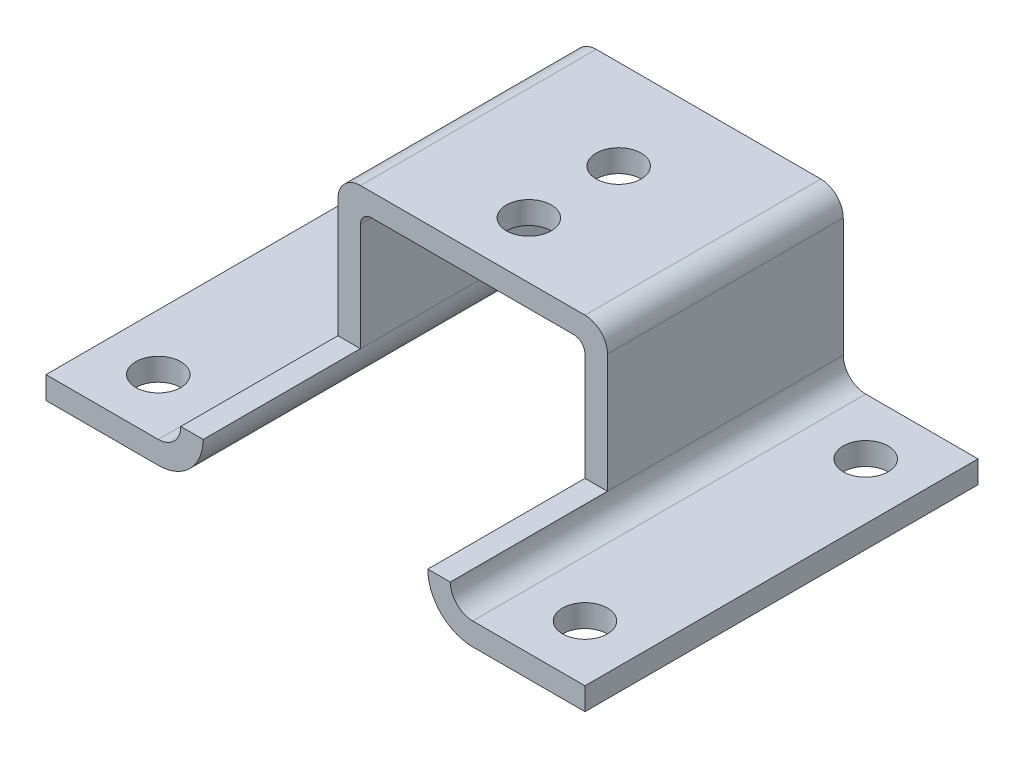
SolidWorks part; units mm, degrees
ref_plane "Front Plane" through (0, 0, 0) normal (0, 0, 1) x (1, 0, 0)
ref_plane "Top Plane" through (0, 0, 0) normal (0, 1, 0) x (1, 0, 0)
ref_plane "Right Plane" through (0, 0, 0) normal (1, 0, 0) x (0, 0, -1)
sketch "Sketch2" plane through (0, 0, 0) normal (0, 0, 1) x (1, 0, 0)
  line L0 (-24, 16.2679) -> (-24, 18.2679)
  line L1 (-24, 18.2679) -> (-14, 18.2679)
  line L2 (-12, 20.2679) -> (-12, 30.8537)
  line L3 (-10, 32.8537) -> (10, 32.8537)
  line L4 (0, 47.6341) -> (0, -40.9024) construction
  line L5 (-24, 16.2679) -> (-14, 16.2679)
  line L6 (-10, 20.2679) -> (-10, 29.8537)
  line L7 (-9, 30.8537) -> (9, 30.8537)
  line L8 (10, 20.2679) -> (10, 29.8537)
  line L9 (24, 16.2679) -> (14, 16.2679)
  line L10 (12, 20.2679) -> (12, 30.8537)
  line L11 (24, 18.2679) -> (14, 18.2679)
  line L12 (24, 16.2679) -> (24, 18.2679)
  line L13 (-12, 20.2679) -> (-10, 20.2679)
  line L14 (12, 20.2679) -> (10, 20.2679)
  arc A0 (-12, 30.8537) -> (-10, 32.8537) centre (-10, 30.8537) cw
  arc A1 (-14, 18.2679) -> (-12, 20.2679) centre (-14, 20.2679) ccw
  arc A2 (-14, 16.2679) -> (-10, 20.2679) centre (-14, 20.2679) ccw
  arc A3 (-10, 29.8537) -> (-9, 30.8537) centre (-9, 29.8537) cw
  arc A4 (10, 29.8537) -> (9, 30.8537) centre (9, 29.8537) ccw
  arc A5 (14, 16.2679) -> (10, 20.2679) centre (14, 20.2679) cw
  arc A6 (14, 18.2679) -> (12, 20.2679) centre (14, 20.2679) cw
  arc A7 (12, 30.8537) -> (10, 32.8537) centre (10, 30.8537) ccw
  point P9 (-12, 32.8537)
  point P13 (-11.4142, 32.2679)
  point P22 (0, 32.8537)
  point P23 (0, 30.8537)
  point P34 (12, 32.8537)
  dimension "D3" = 2
  dimension "D7" = 4
  dimension "D8" = 1
  dimension "D1" = 12
  dimension "D2" = 2
  dimension "D4" = 16
  dimension "D5" = 2
  dimension "D6" = 2
extrude "Boss-Extrude1" add sketch "Sketch2" along normal blind 35 contours L11 A6 L14 A5 L9 L12 | L5 A2 L13 A1 L1 L0 region at (-16.7641, 17.5944, 0) region at (16.7641, 17.5944, 0)
extrude "Boss-Extrude2" add sketch "Sketch2<3>" along normal blind 21 contours L3 L4 L7 A4 L8 L14 L10 A7 | L4 L3 A0 L2 L13 L6 A3 L7 region at (-11, 20.4418, 0) region at (0.1739, 31.8537, 0)
sketch "Sketch2<3>" plane through (0, 0, 0) normal (0, 0, 1) x (1, 0, 0) same geometry as "Sketch2"
sketch "Sketch3" plane through (0, 32.8537, 0) normal (0, 1, 0) x (1, 0, 0)
  line L0 (-10, 0) -> (10, 0) construction
  line L1 (-24, 0) -> (-14, 0) construction
  circle A0 centre (0, -8) radius 2
  circle A1 centre (0, -16) radius 2
  circle A2 centre (-19, -5) radius 2
  circle A3 centre (-19, -30) radius 2
  circle A4 centre (19, -5) radius 2
  circle A5 centre (19, -30) radius 2
  point P8 (-18.6022, -3.8765)
  point P11 (-17.9911, -29.787)
  point P14 (19.1636, -3.8765)
  point P17 (19.1636, -29.1147)
  point P21 (0, 0)
  point P22 (0, 0)
  point P23 (0, 0)
  point P24 (0, 0)
  dimension "D3" = 4
  dimension "D4" = 4
  dimension "D1" = 8
  dimension "D2" = 16
  dimension "D5" = 25
  dimension "D6" = 5
  dimension "D7" = 19
  dimension "D8" = 38
extrude "Cut-Extrude1" cut sketch "Sketch3" against normal through all contours A0 | A1 | A2 | A3 | A5 | A4 region at (0, 32.8537, 8) region at (0, 32.8537, 16) region at (-19, 32.8537, 5) region at (-19, 32.8537, 30) region at (19, 32.8537, 5) region at (19, 32.8537, 30)
